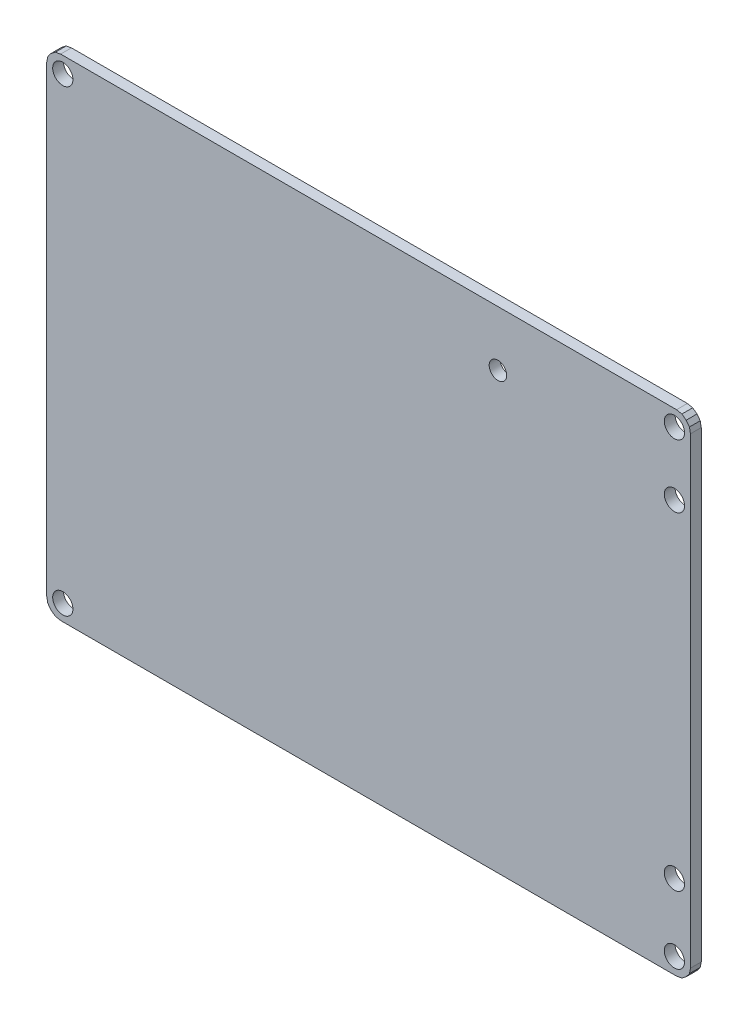
SolidWorks part; units mm, degrees
ref_plane "Спереди" through (0, 0, 0) normal (0, 0, 1) x (1, 0, 0)
ref_plane "Сверху" through (0, 0, 0) normal (0, 1, 0) x (1, 0, 0)
ref_plane "Справа" through (0, 0, 0) normal (1, 0, 0) x (0, 0, -1)
sketch "Эскиз1" plane through (0, 0, 0) normal (0, 0, 1) x (1, 0, 0)
  line L0 (-45.6406, 36.3537) -> (45.6406, 36.3537)
  line L1 (47.5456, 35.0837) -> (47.7044, 34.29)
  line L2 (47.0694, 35.7187) -> (47.5456, 35.0837)
  line L3 (46.4344, 36.195) -> (47.0694, 35.7187)
  line L4 (45.6406, 36.3537) -> (46.4344, 36.195)
  line L5 (47.7044, 34.29) -> (47.7044, -34.29)
  line L6 (-46.4344, 36.195) -> (-45.6406, 36.3537)
  line L7 (-47.0694, 35.7187) -> (-46.4344, 36.195)
  line L8 (-47.5456, 35.0837) -> (-47.0694, 35.7187)
  line L9 (-47.7044, 34.29) -> (-47.5456, 35.0837)
  line L10 (-47.7044, -34.29) -> (-47.7044, 34.29)
  line L11 (-47.5456, -35.0837) -> (-47.7044, -34.29)
  line L12 (-47.0694, -35.7187) -> (-47.5456, -35.0837)
  line L13 (-46.4344, -36.195) -> (-47.0694, -35.7187)
  line L14 (-45.6406, -36.3537) -> (-46.4344, -36.195)
  line L15 (45.6406, -36.3537) -> (-45.6406, -36.3537)
  line L16 (46.4344, -36.195) -> (45.6406, -36.3537)
  line L17 (47.0694, -35.7187) -> (46.4344, -36.195)
  line L18 (47.5456, -35.0837) -> (47.0694, -35.7187)
  line L19 (47.7044, -34.29) -> (47.5456, -35.0837)
  circle A0 centre (19.1694, 28.165) radius 1.3
  circle A1 centre (45.3231, 24.6063) radius 1.5
  circle A2 centre (45.3231, 33.9725) radius 1.5
  circle A3 centre (-45.3229, 33.9727) radius 1.5
  circle A4 centre (-45.3231, -33.9725) radius 1.5
  circle A5 centre (45.3231, -33.9725) radius 1.5
  circle A6 centre (45.3231, -23.9713) radius 1.5
extrude "Бобышка-Вытянуть1" add sketch "Эскиз1" along normal blind 1.6
